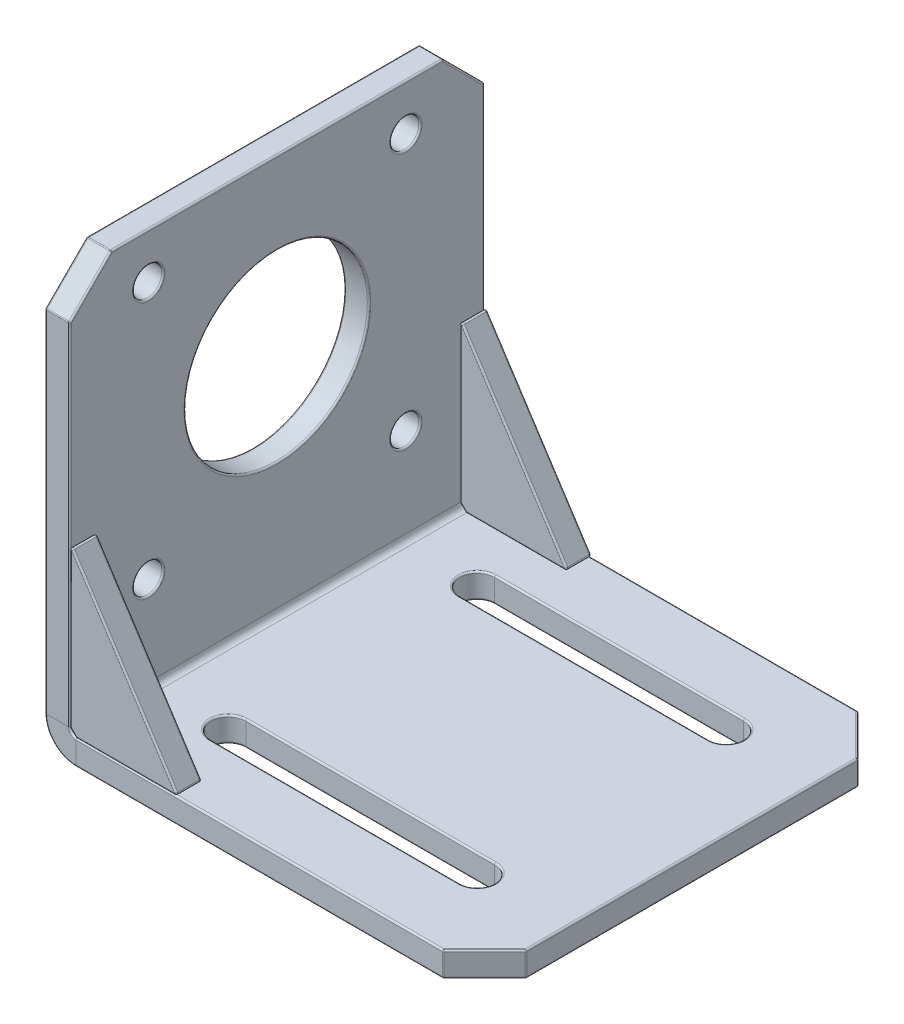
SolidWorks part; units mm, degrees
note: The reader was unsure of these and kept them because the rebuilt part matched: flange length of "Bordo-Flangia1".
ref_plane "Piano frontale" through (0, 0, 0) normal (0, 0, 1) x (1, 0, 0)
ref_plane "Piano superiore" through (0, 0, 0) normal (0, 1, 0) x (1, 0, 0)
ref_plane "Piano destro" through (0, 0, 0) normal (1, 0, 0) x (0, 0, -1)
sketch "Schizzo1" plane through (0, 0, 0) normal (0, 0, 1) x (1, 0, 0)
  line L0 (0, 0) -> (53, 0)
  dimension "D1" = 53
base flange "Base-Flangia1" sketch "Schizzo1" end condition mid plane depth 50 reverse direction no thickness 3 reverse thickness direction no bend radius 0.7366
edge flange "Bordo-Flangia1" sketch "Schizzo8" flange angle 90 flange length 51 flange position material inside bend radius 0.7366 thickness 3 parameters "D6"=10
sketch "Schizzo8" plane through (0, 0, 0) normal (-1, 0, 0) x (0, 0, 1)
  line L0 (25, 0) -> (-25, 0) construction
  line L1 (25, 0) -> (-25, 0)
  line L2 (-25, 0) -> (-25, 48)
  line L3 (-25, 48) -> (25, 48)
  line L4 (25, 48) -> (25, 0)
  line L5 (25, -3) -> (-25, -3) construction
  point P6 (0, -3)
  dimension "D1" = 51
bend "PiegaturaBordo1" bend radius 0.7366 bend angle 90 parameters "D5"=1
sketch "Schizzo10" plane through (3, 0, 0) normal (1, 0, 0) x (0, 0, -1)
  line L0 (0, 48) -> (0, 0.7366) construction
  line L1 (-25, 48) -> (25, 48) construction
  line L2 (25, 0.7366) -> (-25, 0.7366) construction
  line L3 (25, 27) -> (-25, 27) construction
  line L4 (25, 48) -> (25, 0.7366) construction
  line L5 (-25, 0.7366) -> (-25, 48) construction
  circle A0 centre (0, 27) radius 11.05
  circle A1 centre (-15.5, 42.5) radius 1.75
  circle A2 centre (15.5, 42.5) radius 1.75
  circle A3 centre (-15.5, 11.5) radius 1.75
  circle A4 centre (15.5, 11.5) radius 1.75
  dimension "D1" = 22.1
  dimension "D2" = 21
  dimension "D3" = 3.5
  dimension "D4" = 31
  dimension "D5" = 31
extrude "Taglio-Estrusione1" cut sketch "Schizzo10" against normal through all normal cut yes
sketch "Schizzo12" plane through (0, 0, 0) normal (0, 1, 0) x (1, 0, 0)
  line L0 (53, 0) -> (0, 0) construction
  line L1 (53, -25) -> (53, 25) construction
  line L2 (53, 15.1) -> (0, 15.1) construction
  line L3 (53, -14.9) -> (0, -14.9) construction
  line L4 (27, 22.993) -> (27, -20.2654) construction
  line L5 (12, 22.993) -> (12, -20.2654) construction
  line L6 (42, 22.993) -> (42, -20.2654) construction
  line L7 (42, 15.1) -> (12, 15.1) construction
  line L8 (42, 13) -> (12, 13)
  line L9 (42, 17.2) -> (12, 17.2)
  line L10 (42, -14.9) -> (12, -14.9) construction
  line L11 (42, -17) -> (12, -17)
  line L12 (42, -12.8) -> (12, -12.8)
  arc A0 (42, 13) -> (42, 17.2) centre (42, 15.1) ccw
  arc A1 (12, 17.2) -> (12, 13) centre (12, 15.1) ccw
  arc A2 (42, -17) -> (42, -12.8) centre (42, -14.9) ccw
  arc A3 (12, -12.8) -> (12, -17) centre (12, -14.9) ccw
  point P17 (27, 15.1)
  point P22 (27, -14.9)
  dimension "D5" = 11
  dimension "D3" = 4.2
  dimension "D2" = 30
  dimension "D1" = 30
extrude "Taglio-Estrusione3" cut sketch "Schizzo12" against normal through all normal cut yes
sketch "Schizzo15" plane through (0, 0, 0) normal (0, 0, 1) x (1, 0, 0)
  line L0 (0, 20) -> (5.1835, 20) construction
  line L1 (0, 0.7366) -> (0, 48) construction
  line L2 (16, -3) -> (16, 2.1352) construction
  line L3 (3.7366, -3) -> (53, -3) construction
  line L4 (13.7349, 0) -> (-1.1225, 0) construction
  line L5 (42, 0) -> (12, 0) construction
  line L6 (3, 20) -> (3, -3.5666) construction
  line L7 (3, 0.7366) -> (3, 48) construction
  line L8 (3, 20) -> (16, 0)
  line L9 (16, 0) -> (3.7366, 0)
  line L10 (3.7366, 0) -> (3, 0.7366)
  line L11 (3, 0.7366) -> (3, 20)
  dimension "D1" = 20
  dimension "D2" = 13
extrude "Estrusione-Estrusione3" add sketch "Schizzo15" against normal blind 3 from surface at 25 separate body starting at face at (1.5, 24.3683, 25)
mirror "Specchia5" about plane through (0, 0, 0) normal (0, 0, 1) of bodies 109
chamfer "Smusso1" distance 5 angle 45 4 edges at (53, -1.5, 25) (53, -1.5, -25) (1.5, 48, -25) (1.5, 48, 25)
fillet "Raccordo1" radius 0.2 58 edges at (53, 0, 0) (53, -3, 0) (53, -1.5, -20) (53, -1.5, 20) (50.5, -3, -22.5) (50.5, -3, 22.5) (48, -1.5, 25) (50.5, 0, -22.5) (50.5, 0, 22.5) (48, -1.5, -25) (0, 21.8683, -25) (3, 21.8683, -25) (1.5, 43, -25) (3, 48, 0) (25.8683, -3, -25) (3, 45.5, 22.5) (3, 45.5, -22.5) (0, 48, 0) (1.5, 48, 20) (1.5, 48, -20) (25.8683, 0, -25) (0, 45.5, 22.5) (0, 45.5, -22.5) (1.5, 43, 25) (25.8683, -3, 25) (25.8683, 0, 25) (1.0944, -1.9056, -25) (1.0944, -1.9056, 25) (3.2157, 0.2157, -25) (3.2157, 0.2157, 25) (3, 21.8683, 25) (0, 21.8683, 25) (0, 13.25, -15.5) (3, 13.25, -15.5) (0, 9.75, 15.5) (3, 9.75, 15.5) (0, 40.75, -15.5) (3, 40.75, -15.5) (0, 44.25, 15.5) (3, 44.25, 15.5) (0, 38.05, 0) (3, 38.05, 0) (44.1, -3, -15.1) (27, -3, -13) (9.9, -3, -15.1) (27, -3, -17.2) (44.1, 0, -15.1) (27, 0, -17.2) (9.9, 0, -15.1) (27, 0, -13) (44.1, -3, 14.9) (27, -3, 17) (9.9, -3, 14.9) (27, -3, 12.8) (44.1, 0, 14.9) (27, 0, 12.8) (9.9, 0, 14.9) (27, 0, 17)
fillet "Raccordo2" radius 0.2 10 edges at (3.3683, 0.3683, -22) (3, 10.3683, -22) (9.8683, 0, -22) (16, 0, -23.5) (9.5, 10, -22) (3, 20, -23.5) (9.5, 10, -25) (3, 10.3683, -25) (3.3683, 0.3683, -25) (9.8683, 0, -25)
fillet "Raccordo3" radius 0.2 10 edges at (3.3683, 0.3683, 25) (3, 10.3683, 25) (9.8683, 0, 25) (3, 20, 23.5) (16, 0, 23.5) (9.5, 10, 25) (9.5, 10, 22) (3, 10.3683, 22) (3.3683, 0.3683, 22) (9.8683, 0, 22)
sketch "Linee di piegatura1" [suppressed] plane through (0, 0, 0) normal (0, 1, 0) x (1, 0, 0)
sketch "Casella di contorno1" [suppressed] plane through (0, 0, 0) normal (0, 1, 0) x (1, 0, 0)
sheet metal parameters "Lamiera1" thickness 3 parameters "D1"=0.7366
flat pattern "Ripetizione piatta1" [suppressed]
sketch "Linee di piegatura2" plane through (0, 0, 0) normal (0, 1, 0) x (1, 0, 0)
sketch3d "Casella di contorno2" [suppressed]
  line L0 (0, 41.3, 0) -> (0, 0, 0) construction
  line L1 (35, 41.3, 0) -> (35, 0, 0) construction
  line L2 (0, 41.3, 0) -> (35, 41.3, 0) construction
  line L3 (0, 0, 0) -> (35, 0, 0) construction
sheet metal parameters "Lamiera2" thickness 3 parameters "D1"=0.7366
flat pattern "Ripetizione piatta1"
sketch "Linee di piegatura2" plane through (0, 0, 0) normal (0, 1, 0) x (1, 0, 0)
  line L0 (1.98, -25) -> (1.98, 25) construction
  line L1 (1.98, -25) -> (1.98, 25) construction
sketch3d "Casella di contorno2" [suppressed]
  line L0 (53, 0, 0) -> (-47.04, 0, 0) construction
  line L1 (53, 50, 0) -> (-47.04, 50, 0) construction
  line L2 (53, 0, 0) -> (53, 50, 0) construction
  line L3 (-47.04, 0, 0) -> (-47.04, 50, 0) construction
bend of the flat pattern "Appiattito-<PiegaturaBordo1>1"
sheet metal parameters "Lamiera3" thickness 3 parameters "D1"=0.7366
flat pattern "Ripetizione piatta1"
sketch "Linee di piegatura2" plane through (0, 0, 0) normal (0, 1, 0) x (1, 0, 0)
  line L0 (1.98, -25) -> (1.98, 25) construction
  line L1 (1.98, -25) -> (1.98, 25) construction
sketch3d "Casella di contorno2" [suppressed]
  line L0 (53, 0, 0) -> (-47.04, 0, 0) construction
  line L1 (53, 50, 0) -> (-47.04, 50, 0) construction
  line L2 (53, 0, 0) -> (53, 50, 0) construction
  line L3 (-47.04, 0, 0) -> (-47.04, 50, 0) construction
bend of the flat pattern "Appiattito-<PiegaturaBordo1>1"
sheet metal parameters "Lamiera11" thickness 3 parameters "D1"=0.7366
flat pattern "Ripetizione piatta1"
sketch "Linee di piegatura2" plane through (0, 0, 0) normal (0, 1, 0) x (1, 0, 0)
  line L0 (1.98, -24.8) -> (1.98, 24.8) construction
  line L1 (1.98, -24.8) -> (1.98, 24.8) construction
sketch3d "Casella di contorno2" [suppressed]
  line L0 (-47.04, 0, 0) -> (53, 0, 0) construction
  line L1 (-47.04, 50, 0) -> (53, 50, 0) construction
  line L2 (-47.04, 0, 0) -> (-47.04, 50, 0) construction
  line L3 (53, 0, 0) -> (53, 50, 0) construction
bend of the flat pattern "Appiattito-<PiegaturaBordo1>1"
